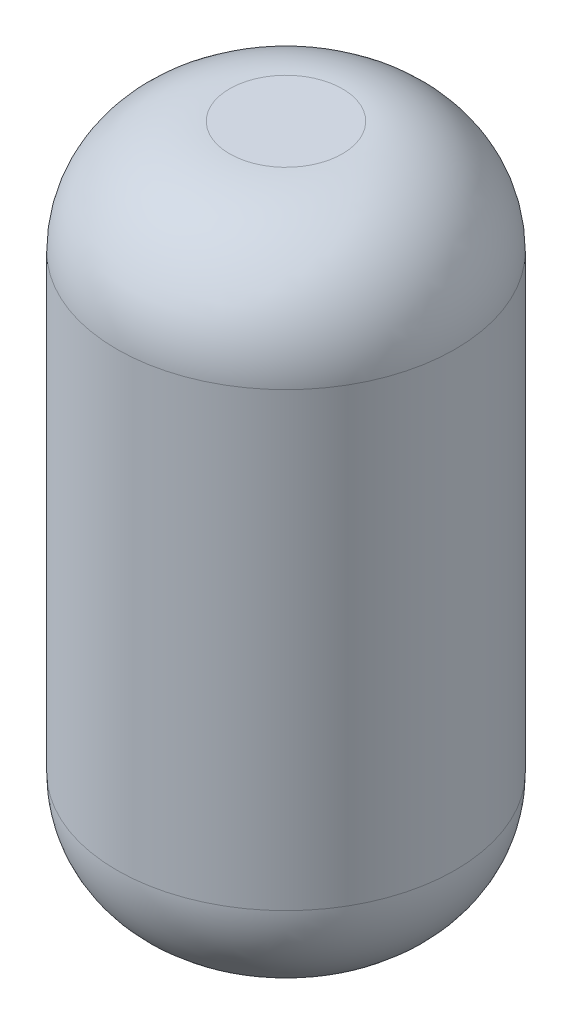
SolidWorks part; units mm, degrees
ref_plane "Plane1" through (0, 0, 0) normal (0, 0, 1) x (1, 0, 0)
ref_plane "Plane2" through (0, 0, 0) normal (0, 1, 0) x (1, 0, 0)
ref_plane "Plane3" through (0, 0, 0) normal (1, 0, 0) x (0, 0, -1)
sketch "Sketch2" plane through (0, 0, 0) normal (0, 1, 0) x (1, 0, 0)
  circle A0 centre (0, 0) radius 9.525
  dimension "D1" = 19.05
extrude "Base-Extrude" add sketch "Sketch2" along normal blind 38.1
fillet "Fillet1" radius 6.35 2 edges at (0, 38.1, 9.525) (0, 0, 9.525)
sketch "Sketch3" plane through (0, 38.1, 0) normal (0, 1, 0) x (-1, 0, 0)
  point P0 (0, 0)
ref_point "Point1"
